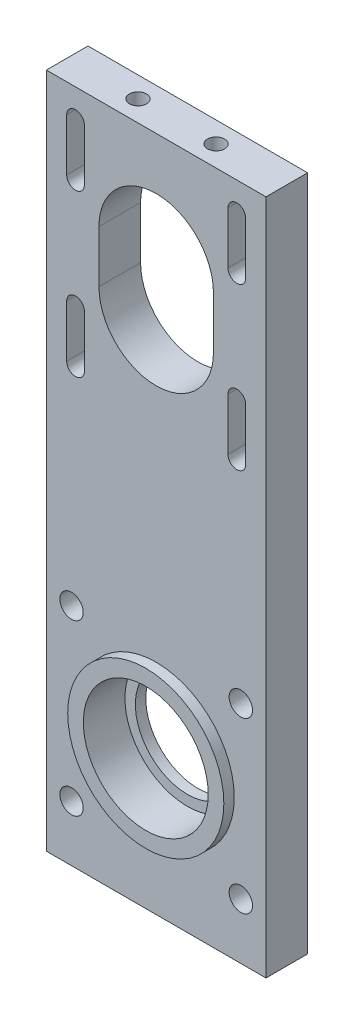
SolidWorks part; units mm, degrees
material "6061-T6 (SS)"
ref_plane "前基準面" through (0, 0, 0) normal (0, 0, 1) x (1, 0, 0)
ref_plane "上基準面" through (0, 0, 0) normal (0, 1, 0) x (1, 0, 0)
ref_plane "右基準面" through (0, 0, 0) normal (1, 0, 0) x (0, 0, -1)
sketch "草圖1" plane through (0, 0, 0) normal (0, 0, 1) x (1, 0, 0)
  line L1 (-21.1, -30) -> (21.1, -30)
  line L2 (-21.1, -30) -> (-21.1, 30)
  line L3 (-21.1, 30) -> (21.1, 30)
  line L4 (21.1, -30) -> (21.1, 30)
  line L5 (-21.1, -30) -> (21.1, 30) construction
  line L6 (-21.1, 30) -> (21.1, -30) construction
  point P0 (0, 0)
  dimension "D1" = 42.2
  dimension "D2" = 60
extrude "填料-伸長1" add sketch "草圖1" along normal mid plane 8
sketch "草圖5" plane through (0, 0, 4) normal (0, 0, 1) x (1, 0, 0)
  circle A0 centre (0, -3) radius 15
  dimension "D1" = 30
  dimension "D2" = 3
extrude "填料-伸長3" add sketch "草圖5" along normal blind 2
sketch "草圖6" plane through (0, 0, 6) normal (0, 0, 1) x (1, 0, 0)
  circle A0 centre (0, -3) radius 10
  dimension "D1" = 20
  dimension "D2" = 3
extrude "除料-伸長3" cut sketch "草圖6" against normal through all
sketch "草圖7" plane through (0, 0, 6) normal (0, 0, 1) x (1, 0, 0)
  circle A0 centre (0, -3) radius 12
  dimension "D1" = 24
  dimension "D2" = 3
extrude "除料-伸長4" cut sketch "草圖7" against normal blind 8
sketch "草圖8" plane through (0, 30, 0) normal (0, 1, 0) x (1, 0, 0)
  line L1 (-21.1, 4) -> (21.1, 4)
  line L2 (-21.1, 4) -> (-21.1, -4)
  line L3 (-21.1, -4) -> (21.1, -4)
  line L4 (21.1, 4) -> (21.1, -4)
extrude "填料-伸長4" add sketch "草圖8" along normal blind 70
sketch "草圖9" plane through (0, 0, -4) normal (0, 0, -1) x (-1, 0, 0)
  line L0 (0, 100) -> (0, 79) construction
  line L1 (-21.1, 100) -> (21.1, 100) construction
  line L2 (0, 79) -> (0, 69) construction
  line L3 (11, 79) -> (11, 69)
  line L4 (-11, 79) -> (-11, 69)
  arc A1 (11, 79) -> (-11, 79) centre (0, 79) ccw
  arc A2 (-11, 69) -> (11, 69) centre (0, 69) ccw
  point P5 (0, 74)
  dimension "D1" = 22
  dimension "D2" = 21
  dimension "D3" = 10
extrude "除料-伸長5" cut sketch "草圖9" against normal through all
hole_wizard "M3 凹頭蓋螺釘的柱孔7" positions "草圖10" profile "草圖11" size "M3" standard "Ansi Metric" slot yes end condition through all
sketch "草圖10" plane through (0, 0, -4) normal (0, 0, 1) x (1, 0, 0)
  line L3 (15.5, 89.5) -> (-15.5, 89.5) construction
  line L4 (15.5, 89.5) -> (15.5, 58.5) construction
  line L5 (15.5, 58.5) -> (-15.5, 58.5) construction
  line L6 (-15.5, 89.5) -> (-15.5, 58.5) construction
  line L7 (15.5, 89.5) -> (-15.5, 58.5) construction
  line L8 (15.5, 58.5) -> (-15.5, 89.5) construction
  line L9 (0, 79) -> (0, 74) construction
  line L11 (15.5, 82.8) -> (15.5, 96.2) construction
  point P117 (15.5, 89.5)
  point P121 (15.5, 58.5)
  point P123 (-15.5, 89.5)
  point P125 (-15.5, 58.5)
  dimension "D1" = 13.4
  dimension "D2" = 31
  dimension "D3" = 5
sketch "草圖11" plane through (15.5, 89.5, -4) normal (1, 0, 0) x (0, 1, 0)
  line L0 (0, 0) -> (0, 10)
  line L1 (0, 10) -> (1.7, 10)
  line L3 (1.7, 10) -> (1.7, 3)
  line L4 (1.7, 3) -> (3.25, 3)
  line L5 (3.25, 3) -> (3.25, 0)
  line L7 (3.25, 0) -> (0, 0)
  line L11 (0, -6.35) -> (0, 107.95) construction
  dimension "貫穿孔直徑" = 3.4
  dimension "貫穿孔深度" = 10
  dimension "柱孔直徑" = 6.5
  dimension "柱孔深度" = 3
hole_wizard "M4 凹頭蓋螺釘的柱孔1" positions "草圖16" profile "草圖17" counterbore size "M4" standard "Ansi Metric" end condition through all
sketch "草圖16" plane through (0, 0, -4) normal (0, 0, -1) x (-1, 0, 0)
  line L1 (-16.2635, -19.2635) -> (16.2635, -19.2635) construction
  line L2 (-16.2635, -19.2635) -> (-16.2635, 13.2635) construction
  line L3 (-16.2635, 13.2635) -> (16.2635, 13.2635) construction
  line L4 (16.2635, -19.2635) -> (16.2635, 13.2635) construction
  line L5 (-16.2635, -19.2635) -> (16.2635, 13.2635) construction
  line L6 (-16.2635, 13.2635) -> (16.2635, -19.2635) construction
  point P1 (16.2635, 13.2635)
  point P122 (-16.2635, -19.2635)
  point P123 (-16.2635, 13.2635)
  point P124 (16.2635, -19.2635)
  point P137 (0, -3)
  dimension "D1" = 46
  dimension "D2" = 3
sketch "草圖17" plane through (-16.2635, 13.2635, -4) normal (1, 0, 0) x (0, 1, 0)
  line L0 (0, 0) -> (0, 10)
  line L1 (0, 10) -> (2.25, 10)
  line L3 (2.25, 10) -> (2.25, 4)
  line L4 (2.25, 4) -> (4, 4)
  line L5 (4, 4) -> (4, 0)
  line L7 (4, 0) -> (0, 0)
  line L11 (0, -6.35) -> (0, 107.95) construction
  dimension "貫穿孔直徑" = 4.5
  dimension "貫穿孔深度" = 10
  dimension "柱孔直徑" = 8
  dimension "柱孔深度" = 4
hole_wizard "M4x0.7 螺紋孔1" positions "草圖14" profile "草圖15" tap size "M4x0.7" standard "Ansi Metric"
sketch "草圖14" plane through (0, -30, 0) normal (0, -1, 0) x (-1, 0, 0)
  line L0 (10, 0) -> (-10, 0) construction
  point P0 (10, 0)
  point P1 (-10, 0)
  point P7 (0, 0)
  dimension "D1" = 20
sketch "草圖15" plane through (-10, -30, 0) normal (1, 0, 0) x (0, 0, -1)
  line L0 (0, 0) -> (0, 11.0914)
  line L1 (0, 11.0914) -> (1.65, 10.1)
  line L2 (1.65, 10.1) -> (1.65, 0)
  line L5 (1.65, 0) -> (0, 0)
  line L10 (0, 11.0914) -> (-1.65, 10.1) construction
  line L11 (0, -6.35) -> (0, 107.95) construction
  dimension "螺孔鑽直徑" = 3.3
  dimension "螺孔鑽深度" = 10.1
  dimension "導頭角度" = 118
hole_wizard "M4x0.7 螺紋孔2" positions "草圖19" profile "草圖20" tap size "M4x0.7" standard "Ansi Metric"
sketch "草圖19" plane through (0, 100, 0) normal (0, 1, 0) x (1, 0, 0)
  line L0 (-7.5, 0) -> (7.5, 0) construction
  line L2 (21.1, 4) -> (-21.1, 4) construction
  line L3 (21.1, -4) -> (21.1, 4) construction
  point P0 (-7.5, 0)
  point P2 (7.5, 0)
  point P13 (0, 4)
  point P14 (0, 0)
  point P18 (21.1, 0)
  dimension "D1" = 15
sketch "草圖20" plane through (-7.5, 100, 0) normal (1, 0, 0) x (0, 0, 1)
  line L0 (0, 0) -> (0, 8.9914)
  line L1 (0, 8.9914) -> (1.65, 8)
  line L2 (1.65, 8) -> (1.65, 0)
  line L5 (1.65, 0) -> (0, 0)
  line L10 (0, 8.9914) -> (-1.65, 8) construction
  line L11 (0, -6.35) -> (0, 107.95) construction
  dimension "螺孔鑽直徑" = 3.3
  dimension "螺孔鑽深度" = 8
  dimension "導頭角度" = 118
cosmetic thread "鑽孔螺紋1"
cosmetic thread "鑽孔螺紋2"
